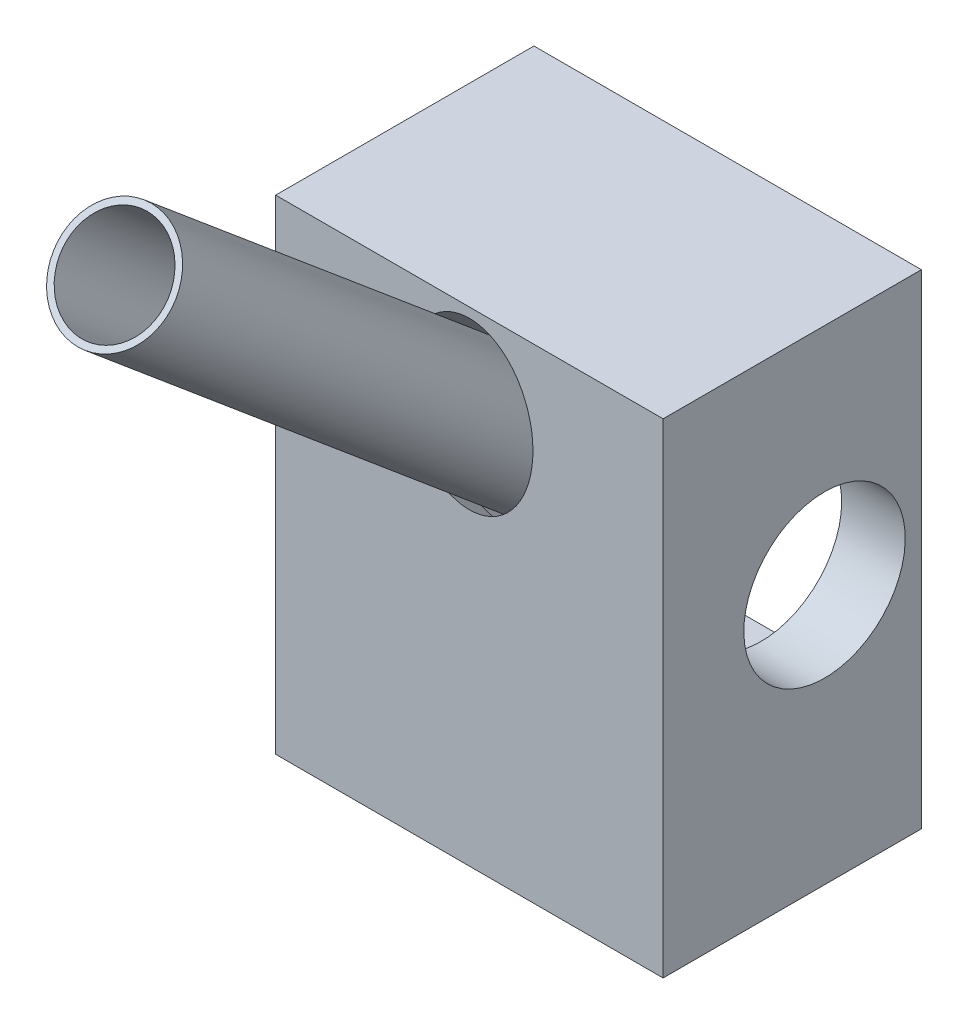
SolidWorks part; units mm, degrees
ref_plane "Front Plane" through (0, 0, 0) normal (0, 0, 1) x (1, 0, 0)
ref_plane "Top Plane" through (0, 0, 0) normal (0, 1, 0) x (1, 0, 0)
ref_plane "Right Plane" through (0, 0, 0) normal (1, 0, 0) x (0, 0, -1)
sketch "Sketch1" plane through (0, 0, 0) normal (0, 0, 1) x (1, 0, 0)
  line L1 (6066.2942, -5703.2258) -> (6096.7742, -5703.2258)
  line L2 (6066.2942, -5703.2258) -> (6066.2942, -5741.3258)
  line L3 (6066.2942, -5741.3258) -> (6096.7742, -5741.3258)
  line L4 (6096.7742, -5703.2258) -> (6096.7742, -5741.3258)
  dimension "D1" = 38.1
  dimension "D2" = 30.48
extrude "Boss-Extrude1" add sketch "Sketch1" along normal blind 20.32 from offset 7.5
sketch "Sketch2" plane through (0, 0, 7.5) normal (0, 0, -1) x (-1, 0, 0)
  line L0 (-6091.7742, -5710.8458) -> (-6096.7742, -5710.8458) construction
  line L1 (-6091.7742, -5710.8458) -> (-6071.3742, -5710.8458)
  line L2 (-6091.7742, -5710.8458) -> (-6091.7742, -5733.7058)
  line L3 (-6091.7742, -5733.7058) -> (-6071.3742, -5733.7058)
  line L4 (-6071.3742, -5710.8458) -> (-6071.3742, -5733.7058)
  line L5 (-6096.7742, -5741.3258) -> (-6096.7742, -5703.2258) construction
  line L6 (-6091.7742, -5710.8458) -> (-6091.7742, -5703.2258) construction
  line L7 (-6096.7742, -5703.2258) -> (-6066.2942, -5703.2258) construction
  line L8 (-6071.3742, -5710.8458) -> (-6066.2942, -5710.8458) construction
  line L9 (-6066.2942, -5703.2258) -> (-6066.2942, -5741.3258) construction
  line L10 (-6091.7742, -5733.7058) -> (-6091.7742, -5741.3258) construction
  line L11 (-6066.2942, -5741.3258) -> (-6096.7742, -5741.3258) construction
  dimension "D1" = 5
  dimension "D2" = 5.08
  dimension "D3" = 7.62
extrude "Cut-Extrude1" cut sketch "Sketch2" against normal blind 17.78
ref_plane "Plane3" through (0, -2342.7368, -2791.965) normal (0, -0.6428, -0.766) x (-1, 0, 0)
sketch "Sketch5" plane through (0, -2342.7368, -2791.965) normal (0, -0.6428, -0.766) x (-1, 0, 0)
  line L0 (-6081.5342, -4392.3948) -> (-6096.7742, -4392.3948) construction
  line L2 (-6081.5342, -4392.3948) -> (-6066.2942, -4392.3948) construction
  line L4 (-6066.2942, -4386.8068) -> (-6066.2942, -4415.9931) construction
  line L5 (-6096.7742, -4415.9931) -> (-6096.7742, -4386.8068) construction
  line L6 (-6081.5342, -4392.3948) -> (-6081.5342, -4386.8068) construction
  line L9 (-6096.7742, -4386.8068) -> (-6066.2942, -4386.8068) construction
  circle A0 centre (-6081.5342, -4392.3948) radius 5
  dimension "D1" = 10
  dimension "D2" = 5.588
extrude "Cut-Extrude2" cut sketch "Sketch5" along normal blind 23
sketch "Sketch10" plane through (0, -2342.7368, -2791.965) normal (0, -0.6428, -0.766) x (-1, 0, 0)
  line L0 (-6081.5342, -4392.3948) -> (-6096.7742, -4392.3948) construction
  line L2 (-6081.5342, -4392.3948) -> (-6066.2942, -4392.3948) construction
  circle A0 centre (-6081.5342, -4392.3948) radius 4.5
  circle A3 centre (-6081.5342, -4392.3948) radius 5 construction
  dimension "D1" = 9
extrude "Boss-Extrude2" add sketch "Sketch10" against normal blind 31.75 and the other way blind 21.59 separate body
sketch "Sketch11" plane through (0, -2356.6146, -2808.5039) normal (0, -0.6428, -0.766) x (1, 0, 0)
  line L0 (6081.5342, 4387.8948) -> (6081.5342, 4392.3948) construction
  line L1 (6086.0342, 4392.3948) -> (6071.072, 4392.3948) construction
  circle A0 centre (6081.5342, 4392.3948) radius 4.5 construction
  circle A1 centre (6081.5342, 4392.3948) radius 4
  dimension "D1" = 8
extrude "Cut-Extrude6" cut sketch "Sketch11" against normal through all
hole_wizard "CSK for M3 Flat Head Machine Screw1" positions "Sketch13" profile "Sketch14" countersink size "M3" standard "ANSI Metric"
sketch "Sketch13" plane through (0, 0, 7.5) normal (0, 0, -1) x (-1, 0, 0)
  line L8 (-6070.1042, -5707.0358) -> (-6070.1042, -5703.2258) construction
  line L9 (-6096.7742, -5703.2258) -> (-6066.2942, -5703.2258) construction
  line L11 (-6070.1042, -5707.0358) -> (-6066.2942, -5707.0358) construction
  line L12 (-6066.2942, -5703.2258) -> (-6066.2942, -5741.3258) construction
  line L14 (-6096.7742, -5707.0358) -> (-6092.9642, -5707.0358) construction
  line L15 (-6096.7742, -5741.3258) -> (-6096.7742, -5703.2258) construction
  line L16 (-6092.9642, -5707.0358) -> (-6092.9642, -5703.2258) construction
  line L18 (-6096.7742, -5737.5158) -> (-6092.9642, -5737.5158) construction
  line L19 (-6092.9642, -5737.5158) -> (-6092.9642, -5741.3258) construction
  line L20 (-6066.2942, -5741.3258) -> (-6096.7742, -5741.3258) construction
  line L22 (-6070.1042, -5737.5158) -> (-6070.1042, -5741.3258) construction
  line L24 (-6070.1042, -5737.5158) -> (-6066.2942, -5737.5158) construction
  point P0 (-6092.9642, -5707.0358)
  point P2 (-6070.1042, -5707.0358)
  point P4 (-6070.1042, -5737.5158)
  point P6 (-6092.9642, -5737.5158)
  point P13 (-6092.9642, -5707.0358)
  dimension "D1" = 3.81
  dimension "D2" = 3.81
sketch "Sketch14" plane through (6092.9642, -5707.0358, 7.5) normal (1, 0, 0) x (0, 1, 0)
  line L0 (0, 0) -> (0, 9.906)
  line L1 (0, 9.906) -> (1.7, 8.8845)
  line L2 (1.7, 8.8845) -> (1.7, 1.45)
  line L3 (1.7, 1.45) -> (3.15, 0)
  line L5 (3.15, 0) -> (0, 0)
  line L6 (-1.7, 1.45) -> (-3.15, 0) construction
  line L10 (0, 9.906) -> (-1.7, 8.8845) construction
  line L11 (0, -6.35) -> (0, 107.95) construction
  dimension "Hole Dia." = 3.4
  dimension "Hole Depth" = 9.906
  dimension "Near C'Sink Dia." = 6.3
  dimension "Near C'Sink Angle" = 90
  dimension "Drill Angle" = 118
sketch "Sketch17" plane through (6096.7742, 0, 0) normal (1, 0, 0) x (0, 0, -1)
  line L0 (-7.5, -5741.3258) -> (-7.5, -5703.2258) construction
  circle A0 centre (-15.12, -5720.8998) radius 6.35
  dimension "D1" = 7.62
  dimension "D2" = 12.7
extrude "Cut-Extrude7" cut sketch "Sketch17" against normal through all
sketch "Sketch19" plane through (0, -5741.3258, 0) normal (0, -1, 0) x (1, 0, 0)
  circle A0 centre (6081.5342, 17.66) radius 0.05
  dimension "D1" = 0.1
extrude "Boss-Extrude3" add sketch "Sketch19" along normal blind 0.1
ref_plane "Plane4" through (6096.7742, -5741.3258, 7.5) normal (0, 1, 0) x (1, 0, 0)
sketch "Sketch29" plane through (0, -5741.3258, 0) normal (0, -1, 0) x (1, 0, 0)
  circle A0 centre (6081.5342, 17.66) radius 6
  dimension "D1" = 12
extrude "Cut-Extrude8" cut sketch "Sketch29" against normal up to surface (7.62 mm away) up to face at (6081.5742, -5733.7058, 16.39)
sketch "Sketch30" plane through (0, -5741.3258, 0) normal (0, -1, 0) x (1, 0, 0)
  line L0 (6072.6442, 11.31) -> (6066.2942, 11.31) construction
  line L1 (6088.5192, 22.867) -> (6092.3292, 22.867)
  line L2 (6088.5192, 22.867) -> (6088.5192, 25.153)
  line L3 (6088.5192, 25.153) -> (6092.3292, 25.153)
  line L4 (6092.3292, 22.867) -> (6092.3292, 25.153)
  line L5 (6088.5192, 22.867) -> (6092.3292, 25.153) construction
  line L6 (6088.5192, 25.153) -> (6092.3292, 22.867) construction
  line L7 (6070.7392, 10.167) -> (6074.5492, 10.167)
  line L8 (6070.7392, 10.167) -> (6070.7392, 12.453)
  line L9 (6070.7392, 12.453) -> (6074.5492, 12.453)
  line L10 (6074.5492, 10.167) -> (6074.5492, 12.453)
  line L11 (6070.7392, 10.167) -> (6074.5492, 12.453) construction
  line L12 (6070.7392, 12.453) -> (6074.5492, 10.167) construction
  line L13 (6066.2942, 27.82) -> (6066.2942, 7.5) construction
  line L14 (6072.6442, 11.31) -> (6072.6442, 7.5) construction
  line L15 (6066.2942, 7.5) -> (6096.7742, 7.5) construction
  line L16 (6090.4242, 24.01) -> (6090.4242, 27.82) construction
  line L17 (6066.2942, 27.82) -> (6096.7742, 27.82) construction
  line L18 (6090.4242, 24.01) -> (6096.7742, 24.01) construction
  line L19 (6096.7742, 27.82) -> (6096.7742, 7.5) construction
  point P0 (6090.4242, 24.01)
  point P5 (6072.6442, 11.31)
  point P21 (6093.8735, 25.3522)
  point P25 (6093.3527, 25.0597)
  point P26 (6091.5747, 25.1365)
  point P27 (6091.2174, 25.0482)
  dimension "D1" = 3.81
  dimension "D2" = 2.286
  dimension "D3" = 3.81
  dimension "D4" = 2.286
  dimension "D5" = 6.35
  dimension "D6" = 3.81
extrude "Boss-Extrude4" add sketch "Sketch30" along normal blind 2.54
